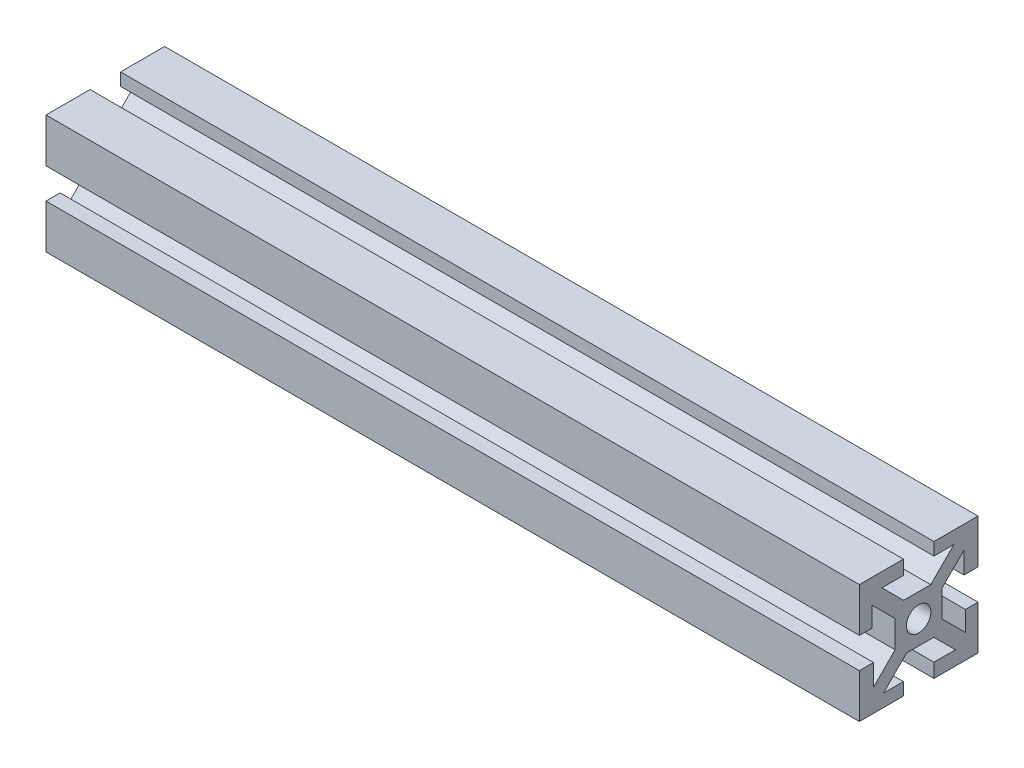
SolidWorks part; units mm, degrees
ref_plane "Front Plane" through (0, 0, 0) normal (0, 0, 1) x (1, 0, 0)
ref_plane "Top Plane" through (0, 0, 0) normal (0, 1, 0) x (1, 0, 0)
ref_plane "Right Plane" through (0, 0, 0) normal (1, 0, 0) x (0, 0, -1)
sketch "Sketch1" plane through (0, 0, 0) normal (1, 0, 0) x (0, 0, -1)
  line L0 (2.5534, 5) -> (7.4749, 9.9215)
  line L1 (-5, 5) -> (5, 5)
  line L2 (-5, 5) -> (-5, -5)
  line L3 (-5, -5) -> (5, -5)
  line L4 (5, 5) -> (5, -5)
  line L5 (-5, 5) -> (5, -5) construction
  line L6 (-5, -5) -> (5, 5) construction
  line L7 (7.4749, 9.9215) -> (9.5962, 7.8001)
  line L8 (9.5962, 7.8001) -> (5, 3.2039)
  line L9 (5, 5) -> (13.6489, 13.6489) construction
  line L10 (7.4749, 9.9215) -> (3.24, 9.9215)
  line L11 (3.24, 9.9215) -> (3.24, 12.5962)
  line L12 (3.24, 12.5962) -> (12.5962, 12.5962)
  line L13 (9.5962, 7.8001) -> (9.5962, 3.24)
  line L14 (9.5962, 3.24) -> (12.5962, 3.24)
  line L15 (12.5962, 3.24) -> (12.5962, 12.5962)
  line L17 (0, 0) -> (0, 24.089) construction
  line L18 (0, 0) -> (23.75, 0) construction
  circle A0 centre (0, 0) radius 2.605
  point P0 (0, 0)
  dimension "D1" = 5.21
  dimension "D2" = 10
  dimension "D3" = 10
  dimension "D4" = 3
  dimension "D5" = 1.27
  dimension "D6" = 6.5
  dimension "D7" = 3.24
  dimension "D8" = 3.24
  dimension "D9" = 3
extrude "Boss-Extrude1" add sketch "Sketch1" along normal blind 172.72 contours L4 L1 L2 L3 A0 | L8 L7 L0 L1 L4 | L14 L15 L12 L11 L10 L7 L13 region at (0, 4.8586, -3.7767) region at (0, 6.7479, -6.3823) region at (0, 9.18, -9.3105)
ref_axis "Axis1" through (0, 0, 0) along (1, 0, 0)
pattern_circular "CirPattern1" count 4 over 360 about axis through (0, 0, 0) along (1, 0, 0) of "Boss-Extrude1"
sketch "Sketch2" plane through (0, 0, 12.5962) normal (0, 0, 1) x (1, 0, 0)
  circle A0 centre (86.36, 0) radius 2.38
  dimension "D1" = 4.76
  dimension "D2" = 86.36
extrude "Cut-Extrude6" cut sketch "Sketch2" against normal blind 8
